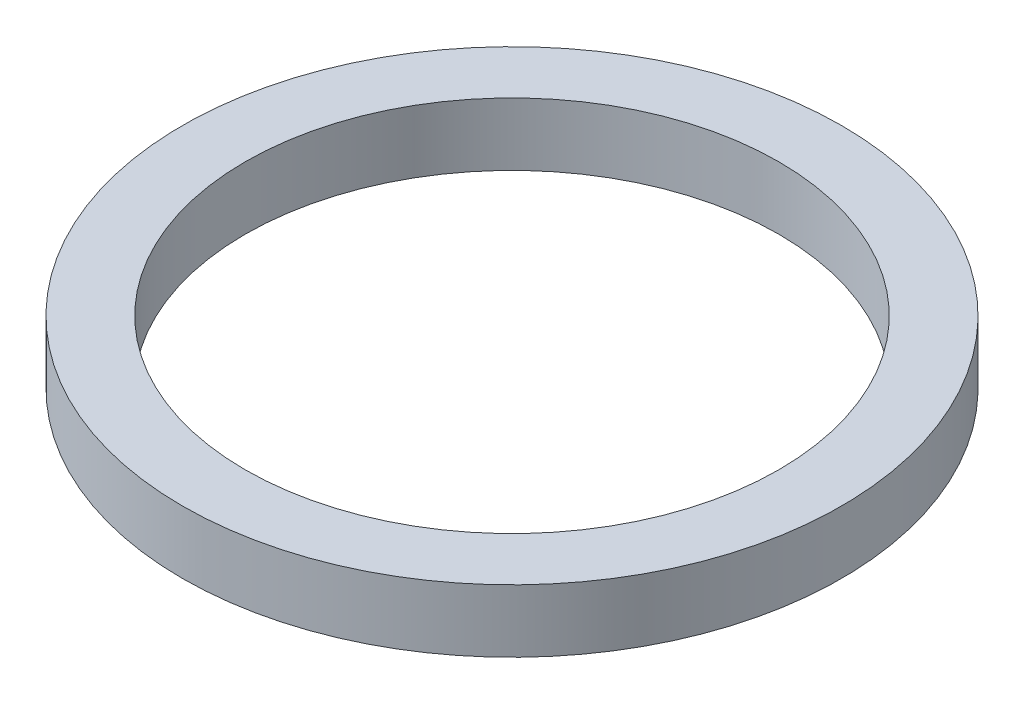
SolidWorks part; units mm, degrees
ref_plane "Front Plane" through (0, 0, 0) normal (0, 0, 1) x (1, 0, 0)
ref_plane "Top Plane" through (0, 0, 0) normal (0, 1, 0) x (1, 0, 0)
ref_plane "Right Plane" through (0, 0, 0) normal (1, 0, 0) x (0, 0, -1)
sketch "Sketch1" plane through (0, 0, 0) normal (0, 1, 0) x (1, 0, 0)
  circle A0 centre (0, 0) radius 52.5
  dimension "FLANGE_OD" = 105
extrude "Boss-Extrude1" add sketch "Sketch1" along normal blind 10
sketch "Sketch2" plane through (0, 0, 0) normal (0, 1, 0) x (1, 0, 0)
  circle A0 centre (0, 0) radius 42.5
  dimension "BORE_D" = 85
extrude "Cut-Extrude1" cut sketch "Sketch2" along normal through all
sketch "Sketch3" plane through (0, 10, 0) normal (0, 1, 0) x (1, 0, 0)
  circle A0 centre (0, 0) radius 23.4045 construction
  circle A1 centre (-23.4045, 0) radius 1.6374
  dimension "BOLT_D" = 3.2748
  dimension "BOLT_PCD" = 46.809
extrude "Cut-Extrude2" cut sketch "Sketch3" against normal blind 8.5721 rebuild error yes
pattern_circular "CirPattern1" count 5 over 360 rebuild error yes
